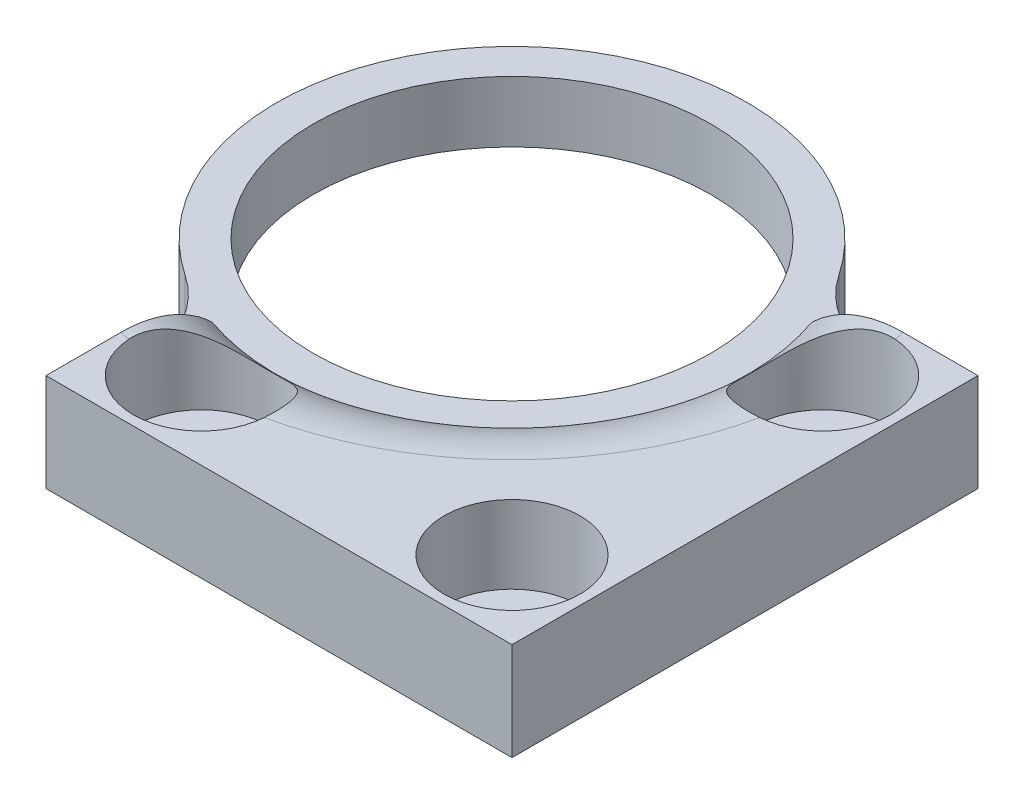
SolidWorks part; units mm, degrees
ref_plane "Front Plane" through (0, 0, 0) normal (0, 0, 1) x (1, 0, 0)
ref_plane "Top Plane" through (0, 0, 0) normal (0, 1, 0) x (1, 0, 0)
ref_plane "Right Plane" through (0, 0, 0) normal (1, 0, 0) x (0, 0, -1)
sketch "Sketch1" plane through (0, 0, 0) normal (0, 1, 0) x (1, 0, 0)
  circle A0 centre (0, 0) radius 16.25
  circle A1 centre (0, 0) radius 19.25
  dimension "D1" = 32.5
  dimension "D2" = 3
extrude "Boss-Extrude1" add sketch "Sketch1" along normal blind 5
sketch "Sketch2" plane through (0, 0, 0) normal (0, 1, 0) x (1, 0, 0)
  line L1 (31.75, -31.75) -> (-6.35, -31.75)
  line L2 (31.75, -31.75) -> (31.75, 6.35)
  line L3 (31.75, 6.35) -> (-6.35, 6.35)
  line L4 (-6.35, -31.75) -> (-6.35, 6.35)
  circle A0 centre (25.4, -25.4) radius 3.175 construction
  circle A1 centre (25.4, 0) radius 3.175 construction
  circle A2 centre (0, -25.4) radius 3.175 construction
  circle A5 centre (0, 0) radius 19.25
  circle A6 centre (0, 0) radius 19.25
  dimension "D1" = 6.35
  dimension "D2" = 6.35
  dimension "D3" = 6.35
  dimension "D4" = 6.35
  dimension "D5" = 0
extrude "Boss-Extrude2" add sketch "Sketch2" along normal blind 8 contours A6 L4 L1 L2 L3 region at (17.5275, 0, 17.5275)
hole_wizard "CBORE for 1/4 Socket Head Cap Screw2" positions "Sketch5" profile "Sketch6" counterbore size "1/4" standard "ANSI Inch" end condition through all
sketch "Sketch5" plane through (0, 8, 0) normal (0, 1, 0) x (1, 0, 0)
  point P0 (0, -25.4)
  point P3 (25.4, -25.4)
  point P6 (25.4, 0)
sketch "Sketch6" plane through (0, 8, 25.4) normal (1, 0, 0) x (0, 0, 1)
  line L0 (0, 0) -> (0, 8)
  line L1 (0, 8) -> (3.3782, 8)
  line L3 (3.3782, 8) -> (3.3782, 6.35)
  line L4 (3.3782, 6.35) -> (5.5562, 6.35)
  line L5 (5.5562, 6.35) -> (5.5562, 0)
  line L7 (5.5562, 0) -> (0, 0)
  line L11 (0, -6.35) -> (0, 107.95) construction
  dimension "Thru Hole Dia." = 6.7564
  dimension "Thru Hole Depth" = 8
  dimension "C'Bore Dia." = 11.1125
  dimension "C'Bore Depth" = 6.35
fillet "Fillet1" radius 10 3 edges at (18.1725, 2.5, -6.35) (-6.35, 2.5, 18.1725) (13.6118, 8, 13.6118)
